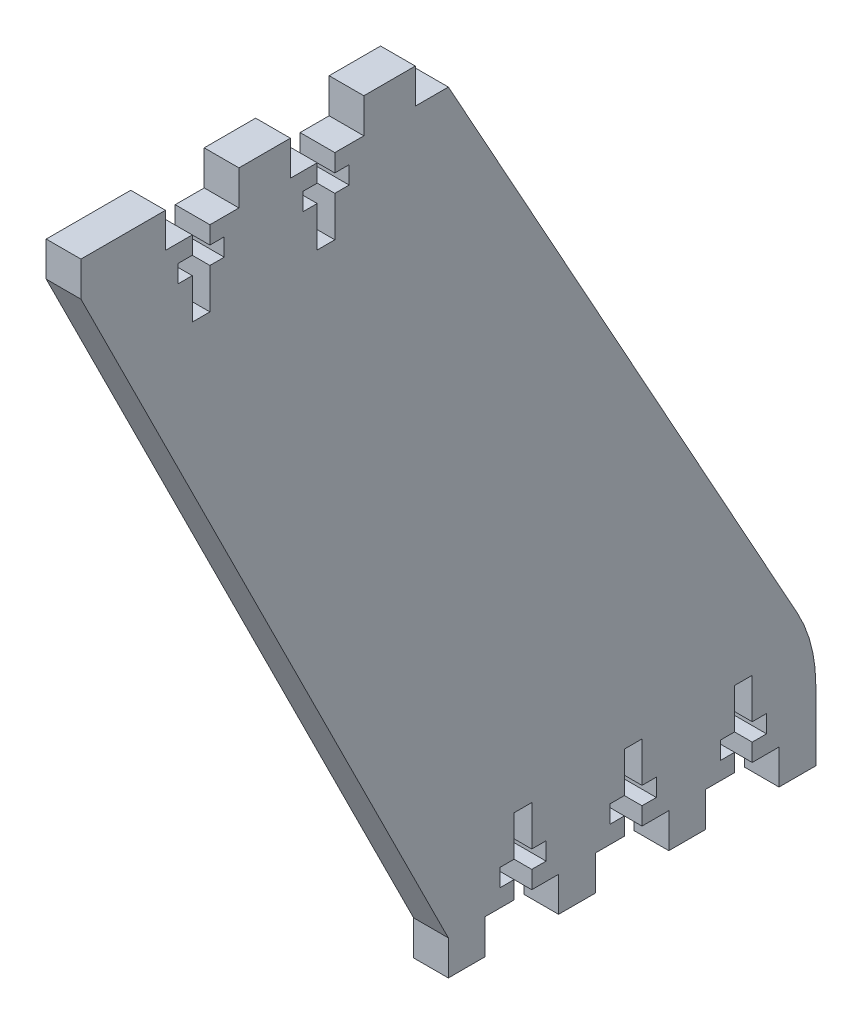
SolidWorks part; units mm, degrees
ref_plane "Front Plane" through (0, 0, 0) normal (0, 0, 1) x (1, 0, 0)
ref_plane "Top Plane" through (0, 0, 0) normal (0, 1, 0) x (1, 0, 0)
ref_plane "Right Plane" through (0, 0, 0) normal (1, 0, 0) x (0, 0, -1)
sketch "Sketch1" plane through (0, 0, 0) normal (1, 0, 0) x (0, 0, -1)
  line L0 (-74.3254, 0) -> (74.3254, 0) construction
  line L1 (-31.75, 0) -> (-95.25, 127.35)
  line L4 (-31.75, 0) -> (0, 17.1799) construction
  line L5 (-95.25, 127.35) -> (-95.25, 133.35)
  line L6 (-95.25, 133.35) -> (-80.645, 133.35)
  line L7 (-80.645, 133.35) -> (-80.645, 127.35)
  line L8 (-80.645, 127.35) -> (-67.945, 127.35)
  line L9 (-67.945, 127.35) -> (-67.945, 133.35)
  line L10 (-67.945, 133.35) -> (-59.055, 133.35)
  line L11 (-59.055, 133.35) -> (-59.055, 127.35)
  line L12 (-59.055, 127.35) -> (-46.355, 127.35)
  line L13 (-46.355, 127.35) -> (-46.355, 133.35)
  line L14 (-46.355, 133.35) -> (-37.465, 133.35)
  line L15 (-37.465, 133.35) -> (-37.465, 127.35)
  line L16 (-37.465, 127.35) -> (-31.75, 127.35)
  line L17 (-31.75, 0) -> (-31.75, -6)
  line L18 (-31.75, -6) -> (-25.4, -6)
  line L19 (-25.4, -6) -> (-25.4, 0)
  line L20 (-25.4, 0) -> (-12.7, 0)
  line L21 (-12.7, 0) -> (-12.7, -6)
  line L22 (-12.7, -6) -> (-6.35, -6)
  line L23 (-6.35, -6) -> (-6.35, 0)
  line L24 (-6.35, 0) -> (6.35, 0)
  line L25 (6.35, 0) -> (6.35, -6)
  line L26 (6.35, -6) -> (12.7, -6)
  line L27 (12.7, -6) -> (12.7, 0)
  line L28 (12.7, 0) -> (25.4, 0)
  line L29 (25.4, 0) -> (25.4, -6)
  line L30 (25.4, -6) -> (31.75, -6)
  line L31 (31.75, -6) -> (31.75, 0)
  line L32 (0, 17.1799) -> (31.75, 0) construction
  line L33 (0, 0) -> (0, 17.1799) construction
  line L34 (-63.5, 133.35) -> (-63.5, 108.2099) construction
  line L35 (31.75, 0) -> (31.75, 6.1358)
  line L36 (28.5696, 18.4423) -> (-31.75, 127.35)
  arc A0 (31.75, 6.1358) -> (28.5696, 18.4423) centre (6.35, 6.1358) ccw
  point P37 (-74.295, 127.35)
  point P38 (-52.705, 127.35)
  point P39 (-19.05, 0)
  point P40 (19.05, 0)
  point P44 (31.75, 12.7)
  line B0 (-18.8595, 13.05) -> (-18.8595, -5.9362) construction
  line B1 (-20.3835, 0) -> (-20.3835, 3.048)
  line B2 (-20.3835, 3.048) -> (-22.86, 3.048)
  line B3 (-22.86, 3.048) -> (-22.86, 6.096)
  line B4 (-22.86, 6.096) -> (-20.3835, 6.096)
  line B5 (-20.3835, 6.096) -> (-20.3835, 13.05)
  line B6 (-20.3835, 13.05) -> (-17.3355, 13.05)
  line B7 (-17.3355, 6.096) -> (-17.3355, 13.05)
  line B8 (-14.859, 6.096) -> (-17.3355, 6.096)
  line B9 (-14.859, 3.048) -> (-14.859, 6.096)
  line B10 (-17.3355, 3.048) -> (-14.859, 3.048)
  line B11 (-17.3355, 0) -> (-17.3355, 3.048)
  line B12 (0.1905, 13.05) -> (0.1905, -5.9362) construction
  line B13 (-1.3335, 0) -> (-1.3335, 3.048)
  line B14 (-1.3335, 3.048) -> (-3.81, 3.048)
  line B15 (-3.81, 3.048) -> (-3.81, 6.096)
  line B16 (-3.81, 6.096) -> (-1.3335, 6.096)
  line B17 (-1.3335, 6.096) -> (-1.3335, 13.05)
  line B18 (-1.3335, 13.05) -> (1.7145, 13.05)
  line B19 (1.7145, 6.096) -> (1.7145, 13.05)
  line B20 (4.191, 6.096) -> (1.7145, 6.096)
  line B21 (4.191, 3.048) -> (4.191, 6.096)
  line B22 (1.7145, 3.048) -> (4.191, 3.048)
  line B23 (1.7145, 0) -> (1.7145, 3.048)
  line B24 (19.2405, 13.05) -> (19.2405, -5.9362) construction
  line B25 (17.7165, 0) -> (17.7165, 3.048)
  line B26 (17.7165, 3.048) -> (15.24, 3.048)
  line B27 (15.24, 3.048) -> (15.24, 6.096)
  line B28 (15.24, 6.096) -> (17.7165, 6.096)
  line B29 (17.7165, 6.096) -> (17.7165, 13.05)
  line B30 (17.7165, 13.05) -> (20.7645, 13.05)
  line B31 (20.7645, 6.096) -> (20.7645, 13.05)
  line B32 (23.241, 6.096) -> (20.7645, 6.096)
  line B33 (23.241, 3.048) -> (23.241, 6.096)
  line B34 (20.7645, 3.048) -> (23.241, 3.048)
  line B35 (20.7645, 0) -> (20.7645, 3.048)
  line B36 (-74.4855, 114.3) -> (-74.4855, 133.2862) construction
  line B37 (-72.9615, 127.35) -> (-72.9615, 124.302)
  line B38 (-72.9615, 124.302) -> (-70.485, 124.302)
  line B39 (-70.485, 124.302) -> (-70.485, 121.254)
  line B40 (-70.485, 121.254) -> (-72.9615, 121.254)
  line B41 (-72.9615, 121.254) -> (-72.9615, 114.3)
  line B42 (-72.9615, 114.3) -> (-76.0095, 114.3)
  line B43 (-76.0095, 121.254) -> (-76.0095, 114.3)
  line B44 (-78.486, 121.254) -> (-76.0095, 121.254)
  line B45 (-78.486, 124.302) -> (-78.486, 121.254)
  line B46 (-76.0095, 124.302) -> (-78.486, 124.302)
  line B47 (-76.0095, 127.35) -> (-76.0095, 124.302)
  line B48 (-52.8955, 114.3) -> (-52.8955, 133.2862) construction
  line B49 (-51.3715, 127.35) -> (-51.3715, 124.302)
  line B50 (-51.3715, 124.302) -> (-48.895, 124.302)
  line B51 (-48.895, 124.302) -> (-48.895, 121.254)
  line B52 (-48.895, 121.254) -> (-51.3715, 121.254)
  line B53 (-51.3715, 121.254) -> (-51.3715, 114.3)
  line B54 (-51.3715, 114.3) -> (-54.4195, 114.3)
  line B55 (-54.4195, 121.254) -> (-54.4195, 114.3)
  line B56 (-56.896, 121.254) -> (-54.4195, 121.254)
  line B57 (-56.896, 124.302) -> (-56.896, 121.254)
  line B58 (-54.4195, 124.302) -> (-56.896, 124.302)
  line B59 (-54.4195, 127.35) -> (-54.4195, 124.302)
  dimension "D2" = 63.5
  dimension "D5" = 6
  dimension "D3" = 63.5
  dimension "D4" = 6
  dimension "D6" = 133.35
  dimension "D7" = 12.7
  dimension "D8" = 63.5
  dimension "D9" = 12.7
  dimension "D10" = 6.35
  dimension "D11" = 12.7
  dimension "D13" = 8.89
  dimension "D14" = 5.715
sketch_block_instance "Block-6-32x0_625 T-Nut block-1"
sketch_block "Block-6-32x0_625 T-Nut block" parameters "D1"=3.048, "D2"=13.05, "D3"=8.001, "D4"=3.048, "D5"=3.048
sketch_block_instance "Block-6-32x0_625 T-Nut block-2"
sketch_block_instance "Block-6-32x0_625 T-Nut block-3"
sketch_block_instance "Block-6-32x0_625 T-Nut block-5"
sketch_block_instance "Block-6-32x0_625 T-Nut block-6" parameters "D12"=25.4, "D1"=141.4375, "D2"=89.2054, "D3"=17.7034, "D4"=8.9474, "D5"=10.3714, "D6"=8.89, "D7"=11.0685, "D8"=24.0265, "D9"=6.0015, "D10"=6.35, "D11"=148.6509, "D13"=8.89, "D14"=5.715, "D15"=1.905
extrude "Boss-Extrude1" add sketch "Sketch1" along normal blind 6 contours L28 L29 L30 L31 L35 A0 L36 L16 L15 L14 L13 L12 L11 L10 L9 L8 L7 L6 L5 L1 L17 L18 L19 L20 region at (0, 63.5922, 30.2578)
